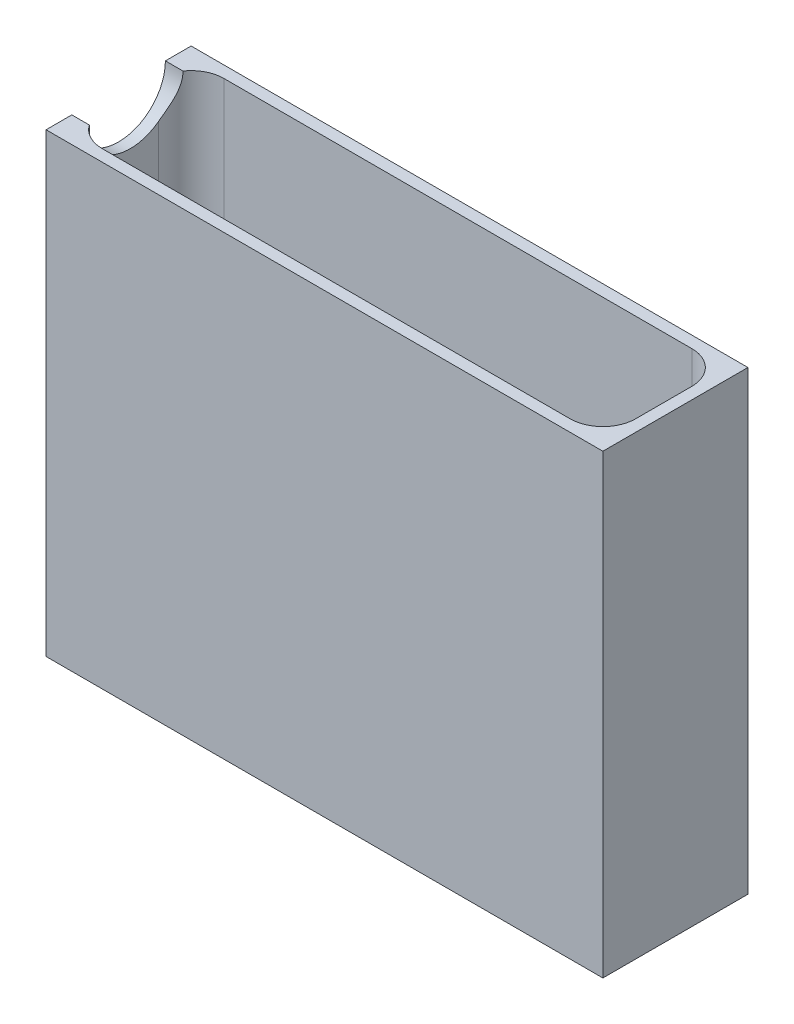
SolidWorks part; units mm, degrees
ref_plane "Front Plane" through (0, 0, 0) normal (0, 0, 1) x (1, 0, 0)
ref_plane "Top Plane" through (0, 0, 0) normal (0, 1, 0) x (1, 0, 0)
ref_plane "Right Plane" through (0, 0, 0) normal (1, 0, 0) x (0, 0, -1)
sketch "Sketch1" plane through (0, 0, 0) normal (0, 1, 0) x (1, 0, 0)
  line L1 (0, 0) -> (-114, 0)
  line L2 (0, 0) -> (0, -26)
  line L3 (0, -26) -> (-114, -26)
  line L4 (-114, 0) -> (-114, -26)
extrude "Extrude-Thin1" add sketch "Sketch1" along normal blind 95 thin thin type one direction wall 2.5
sketch "Sketch2" plane through (0, 0, 0) normal (0, -1, 0) x (1, 0, 0)
  line L1 (-116.5, 28.5) -> (2.5, 28.5)
  line L2 (-116.5, 28.5) -> (-116.5, -2.5)
  line L3 (-116.5, -2.5) -> (2.5, -2.5)
  line L4 (2.5, 28.5) -> (2.5, -2.5)
extrude "Boss-Extrude1" add sketch "Sketch2" along normal blind 2.5
sketch "Sketch3" plane through (-116.5, 0, 0) normal (-1, 0, 0) x (0, 0, 1)
  line L0 (-2.5, 95) -> (28.5, 95) construction
  arc A0 (3, 95) -> (23, 95) centre (13, 95) ccw
extrude "Cut-Extrude1" cut sketch "Sketch3" against normal blind 2.5 and the other way through all
fillet "Fillet2" radius 7 4 edges at (0, 47.5, 26) (0, 47.5, 0) (-114, 47.5, 26) (-114, 47.5, 0)
sketch "Sketch4" plane through (0, 95, 0) normal (0, 1, 0) x (1, 0, 0)
  line L0 (-116.5, 2.5) -> (-114.6624, 0.6624)
sketch "Sketch5" plane through (0, 95, 0) normal (0, 1, 0) x (1, 0, 0)
  line L0 (-116.5, 2.5) -> (-114.6624, 0.6624)
  circle A0 centre (-114.6624, 0.6624) radius 2
